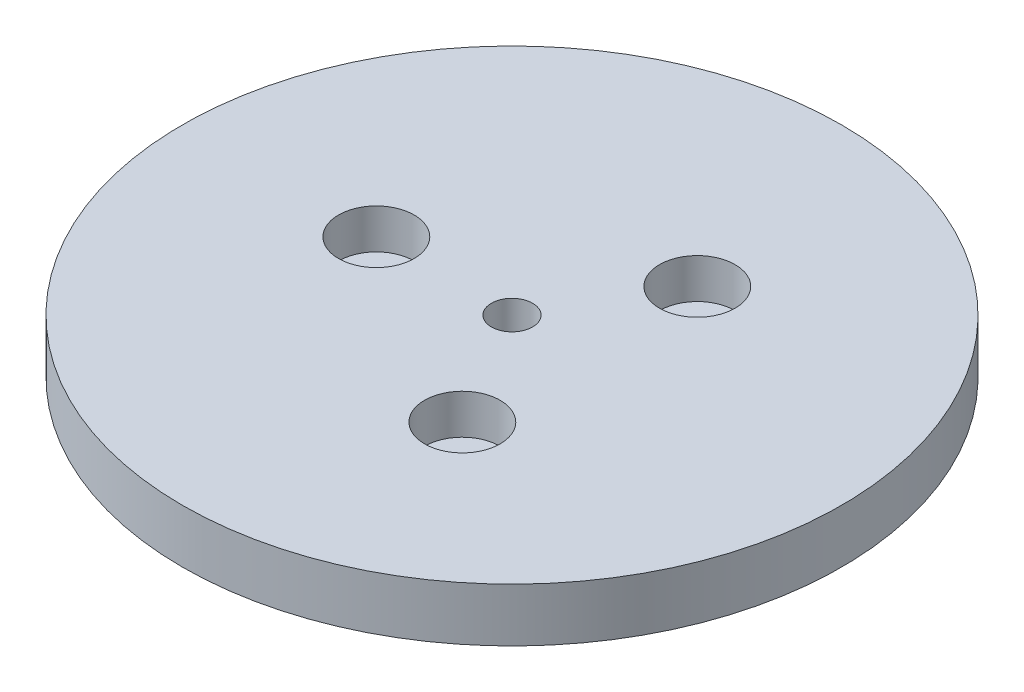
SolidWorks part; units mm, degrees
ref_plane "Front Plane" through (0, 0, 0) normal (0, 0, 1) x (1, 0, 0)
ref_plane "Top Plane" through (0, 0, 0) normal (0, 1, 0) x (1, 0, 0)
ref_plane "Right Plane" through (0, 0, 0) normal (1, 0, 0) x (0, 0, -1)
sketch "Sketch1" plane through (0, 0, 0) normal (0, 1, 0) x (1, 0, 0)
  circle A0 centre (0, 0) radius 80
  dimension "FLANGE_OD" = 160
extrude "Boss-Extrude1" add sketch "Sketch1" along normal blind 13
sketch "Sketch2" plane through (0, 0, 0) normal (0, 1, 0) x (1, 0, 0)
  circle A0 centre (0, 0) radius 5
  dimension "BORE_D" = 10
extrude "Cut-Extrude1" cut sketch "Sketch2" along normal through all
sketch "Sketch3" plane through (0, 13, 0) normal (0, 1, 0) x (1, 0, 0)
  circle A0 centre (0, 0) radius 32.9301 construction
  circle A1 centre (-32.9301, 0) radius 9.1747
  dimension "BOLT_D" = 18.3494
  dimension "BOLT_PCD" = 65.8601
extrude "Cut-Extrude2" cut sketch "Sketch3" against normal blind 9.6688
pattern_circular "CirPattern1" count 3 over 360 about axis through (0, 0, 0) along (0, 1, 0) of "Cut-Extrude2"
